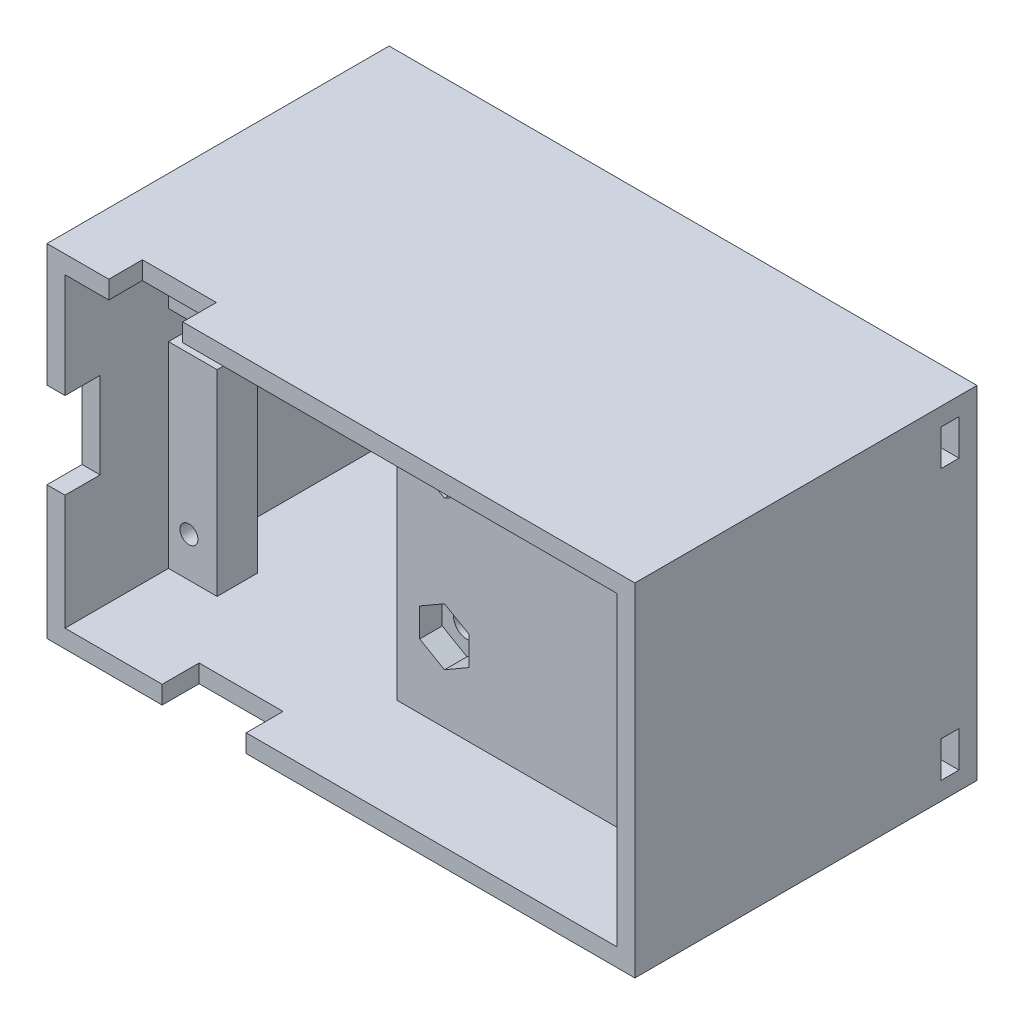
SolidWorks part; units mm, degrees
other "标注1"
sketch "草图16" plane through (3.3763, -43.0665, -26) normal (0.531, -0.7584, -0.3779) x (-0.8474, -0.4776, -0.2321)
other "标注2"
sketch "草图17" plane through (-61.9234, -43.0665, 5.5) normal (-0.5977, -0.3514, 0.7206) x (0.795, -0.3761, 0.4759)
ref_plane "前视基准面" through (0, 0, 0) normal (0, 0, 1) x (1, 0, 0)
ref_plane "上视基准面" through (0, 0, 0) normal (0, 1, 0) x (1, 0, 0)
ref_plane "右视基准面" through (0, 0, 0) normal (1, 0, 0) x (0, 0, -1)
ref_plane "基准面1" through (0, 0, 3.6001) normal (0, 0, 1) x (1, 0, 0)
sketch "草图1" plane through (0, 0, 3.6001) normal (0, 0, 1) x (1, 0, 0)
  line L0 (0.8763, -38.7224) -> (-59.4234, -38.7224) construction
  line L1 (-48.7034, -33.8618) -> (-39.801, -33.8618)
  line L2 (-48.7034, -33.8618) -> (-48.7034, -38.7224)
  line L4 (-39.801, -33.8618) -> (-39.801, -38.7224)
  line L5 (-59.4234, -9.4107) -> (0.8763, -9.4107) construction
  line L7 (-55.7687, -9.4107) -> (-55.7687, -14.2907)
  line L8 (-55.7687, -14.2907) -> (-45.8066, -14.2907)
  line L9 (-45.8066, -9.4107) -> (-45.8066, -14.2907)
  line L10 (-12.699, -17.609) -> (-12.699, -12.109) construction
  line L11 (0.8763, -9.4107) -> (-45.8066, -9.4107)
  line L12 (0.8763, -9.4107) -> (0.8763, -38.7224)
  line L13 (0.8763, -38.7224) -> (-39.801, -38.7224)
  line L14 (-59.4234, -9.4107) -> (-59.4234, -19.2521)
  line L15 (-29.2736, -33.0846) -> (-20.6538, -33.0846)
  line L16 (-29.2736, -33.0846) -> (-29.2736, -36.2921)
  line L17 (-29.2736, -36.2921) -> (-20.6538, -36.2921)
  line L18 (-20.6538, -33.0846) -> (-20.6538, -36.2921)
  line L23 (-12.699, -12.109) -> (-9.399, -12.109)
  line L24 (-12.699, -12.109) -> (-12.699, -17.609)
  line L25 (-12.699, -17.609) -> (-9.399, -17.609)
  line L26 (-9.399, -12.109) -> (-9.399, -17.609)
  line L27 (-48.7034, -38.7224) -> (-59.4234, -38.7224)
  line L28 (-55.7687, -9.4107) -> (-59.4234, -9.4107)
  line L29 (-59.4234, -27.6866) -> (-59.4234, -38.7224)
  line L30 (-59.4234, -19.2521) -> (-54.3557, -19.2521)
  line L32 (-59.4234, -27.6866) -> (-54.3557, -27.6866)
  line L33 (-54.3557, -19.2521) -> (-54.3557, -27.6866)
  circle A0 centre (-57.6581, -36.6498) radius 1
  circle A1 centre (-57.6581, -11.2498) radius 1
  circle A2 centre (-1.016, -11.2498) radius 1
  circle A3 centre (-0.889, -36.8301) radius 1
  circle A4 centre (-4.1259, -29.4689) radius 1.322
  circle A5 centre (-5.9082, -27.2775) radius 0.4462
  circle A6 centre (-4.5737, -26.6799) radius 0.4462
  circle A7 centre (-3.1192, -26.8297) radius 0.4462
  circle A8 centre (-1.9345, -27.6866) radius 0.4462
  circle A9 centre (-1.3369, -29.0211) radius 0.4462
  circle A10 centre (-1.4866, -30.4756) radius 0.4462
  circle A11 centre (-2.3435, -31.6603) radius 0.4462
  circle A12 centre (-3.678, -32.2579) radius 0.4462
  circle A13 centre (-5.1325, -32.1082) radius 0.4462
  circle A14 centre (-6.3173, -31.2513) radius 0.4462
  circle A15 centre (-6.9149, -29.9168) radius 0.4462
  circle A16 centre (-6.7652, -28.4623) radius 0.4462
  point P71 (-4.1259, -29.4689)
  dimension "D1" = 12
ref_plane "基准面2" through (0, 0, -6) normal (0, 0, -1) x (-1, 0, 0)
sketch "草图2" plane through (0, 0, -6) normal (0, 0, -1) x (-1, 0, 0)
  line L0 (29.2736, -9.4107) -> (29.2736, -38.7224) construction
  line L1 (-0.8763, -38.7224) -> (59.4234, -38.7224)
  line L2 (-0.8763, -38.7224) -> (-0.8763, -9.4107)
  line L3 (-0.8763, -9.4107) -> (59.4234, -9.4107)
  line L4 (59.4234, -38.7224) -> (59.4234, -9.4107)
  line L5 (59.4234, -24.0665) -> (-9.3078, -24.0665) construction
  line L6 (-3.3763, -5.0665) -> (61.9234, -43.0665) construction
  line L9 (29.2736, -15.8165) -> (29.2736, -13.1836) construction
  line L10 (27.7854, -15.8165) -> (27.7854, -13.1836)
  line L11 (30.7617, -15.8165) -> (30.7617, -13.1836)
  line L12 (29.2736, -38.7224) -> (29.2736, -43.3487) construction
  line L13 (-3.3763, -43.0665) -> (61.9234, -5.0665) construction
  line L14 (-3.3763, -5.0665) -> (61.9234, -5.0665)
  line L15 (-3.3763, -5.0665) -> (-3.3763, -43.0665)
  line L16 (-3.3763, -43.0665) -> (61.9234, -43.0665)
  line L17 (61.9234, -5.0665) -> (61.9234, -43.0665)
  circle A0 centre (1.016, -11.2498) radius 1
  circle A1 centre (0.889, -36.8301) radius 1
  circle A2 centre (57.6581, -36.6498) radius 1
  circle A3 centre (57.6581, -11.2498) radius 0.9222
  arc A10 (27.7854, -15.8165) -> (30.7617, -15.8165) centre (29.2736, -15.8165) ccw
  arc A11 (30.7617, -13.1836) -> (27.7854, -13.1836) centre (29.2736, -13.1836) ccw
  circle A12 centre (29.2736, -32.3165) radius 1.5
  point P24 (29.2736, -24.0665)
  point P27 (29.2736, -31.5665)
  point P28 (29.2736, -24.0665)
  point P29 (0, 0)
  point P30 (29.2736, -3.8958)
  point P33 (29.2736, -14.5001)
  dimension "D1" = 38
  dimension "D2" = 2.5
  dimension "D3" = 3
  dimension "D4" = 8.25
  dimension "D5" = 2.5
  dimension "D7" = 8.25
extrude "凸台-拉伸2" add sketch "草图2" along normal blind 4.5 separate body contours L17 L14 L15 L16 L4 L1 L2 L3 | L1 L4 L3 L2 A11 L11 A10 L10 A3 A2 A1 A0 region at (-29.281, -24.1116, -6) region at (-29.2736, -5.8221, -6)
sketch "草图3" plane through (0, 0, -6) normal (0, 0, -1) x (-1, 0, 0)
  line L0 (29.2736, -15.8165) -> (29.2736, -10.8487) construction
  line L1 (32.0236, -17.4043) -> (32.0236, -14.2288)
  line L4 (26.5236, -14.2288) -> (26.5236, -17.4043)
  line L5 (26.5236, -17.4043) -> (29.2736, -18.992)
  line L6 (29.2736, -18.992) -> (32.0236, -17.4043)
  line L8 (32.0236, -14.9203) -> (32.0236, -11.7449)
  line L9 (32.0236, -11.7449) -> (29.2736, -10.1572)
  line L10 (29.2736, -10.1572) -> (26.5236, -11.7449)
  line L11 (26.5236, -11.7449) -> (26.5236, -14.9203)
  line L14 (31.8974, -14.9932) -> (32.0236, -14.9203) [skipped]
  line L15 (29.2736, -22.4541) -> (17.663, -22.4541) construction
  line L16 (29.2736, -22.4541) -> (29.2736, -17.3047) construction
  line L17 (26.6497, -14.156) -> (26.5236, -14.2288) [skipped]
  line L18 (26.5236, -14.9203) -> (26.6497, -14.9932) [skipped]
  line L19 (32.0236, -14.2288) -> (31.8974, -14.156) [skipped]
  line L20 (26.5236, -33.9043) -> (29.2736, -35.492)
  line L21 (29.2736, -35.492) -> (32.0236, -33.9043)
  line L22 (32.0236, -33.9043) -> (32.0236, -30.7288)
  line L23 (32.0236, -30.7288) -> (29.2736, -29.1411)
  line L24 (29.2736, -29.1411) -> (26.5236, -30.7288)
  line L25 (26.5236, -30.7288) -> (26.5236, -33.9043)
  arc A0 (26.82, -14.5746) -> (31.7271, -14.5746) centre (29.2736, -15.8165) ccw construction
  arc A1 (31.7271, -14.5746) -> (26.82, -14.5746) centre (29.2736, -13.3326) ccw construction
  circle A2 centre (29.2736, -32.3165) radius 2.75 construction
  circle A3 centre (1.016, -11.2498) radius 1.75
  circle A4 centre (57.6581, -11.2498) radius 1.75
  arc A5 (27.7854, -15.8165) -> (30.7617, -15.8165) centre (29.2736, -15.8165) ccw construction
  circle A6 centre (0.889, -36.8301) radius 1.75
  circle A7 centre (57.6581, -36.6498) radius 1.75
  point P25 (29.2736, -33.8241)
  dimension "D2" = 3.5
  dimension "D1" = 5.5
extrude "切除-拉伸2" cut sketch "草图3" along normal blind 2.5 contours L10 L11 L4 L5 L6 L1 L8 L9 | L24 L25 L20 L21 L22 L23 region at (-29.2736, -14.5746, -6) region at (-29.2736, -32.3165, -6)
sketch "草图5" plane through (0, 0, -10.5) normal (0, 0, -1) x (-1, 0, 0)
  line L0 (29.2736, -7.0665) -> (29.2736, -48.0798) construction
  line L5 (-1.3763, -7.0665) -> (59.9234, -7.0665)
  line L6 (-1.3763, -7.0665) -> (-1.3763, -41.0665)
  line L7 (-1.3763, -41.0665) -> (59.9234, -41.0665)
  line L8 (59.9234, -7.0665) -> (59.9234, -41.0665)
  line L9 (-3.3763, -5.0665) -> (61.9234, -5.0665)
  line L10 (-3.3763, -5.0665) -> (-3.3763, -43.0665)
  line L11 (-3.3763, -43.0665) -> (61.9234, -43.0665)
  line L12 (61.9234, -5.0665) -> (61.9234, -43.0665)
  line L13 (-0.8763, -9.4107) -> (59.4234, -38.7224) construction
  line L14 (-1.3763, -7.0665) -> (59.9234, -41.0665) construction
  line L15 (-3.3763, -5.0665) -> (61.9234, -43.0665) construction
  line L16 (61.9234, -5.0665) -> (-3.3763, -43.0665) construction
  point P12 (29.2736, -24.0665)
  point P13 (29.2736, -24.0665)
  point P18 (29.2736, -24.0665)
  point P19 (0, 0)
  dimension "D1" = 61.2997
  dimension "D2" = 38
  dimension "D3" = 34
  dimension "D4" = 2
extrude "凸台-拉伸3" add sketch "草图5" along normal blind 22 and the other way blind 16
sketch "草图7" plane through (0, -5.0665, 0) normal (0, 1, 0) x (1, 0, 0)
  line L0 (-41.7981, -5.5601) -> (-46.8481, -5.5601) construction
  line L1 (-55.0622, -1.765) -> (-46.8481, -1.765)
  line L2 (-55.0622, -1.765) -> (-55.0622, -5.5601)
  line L3 (-55.0622, -5.5601) -> (-46.8481, -5.5601)
  line L4 (-46.8481, -1.765) -> (-46.8481, -5.5601)
extrude "切除-拉伸4" cut sketch "草图7" against normal blind 3
sketch "草图8" plane through (-61.9234, 0, 0) normal (-1, 0, 0) x (0, 0, 1)
  line L0 (5.6001, -27.6866) -> (5.6001, -38.7224) construction
  line L1 (1.6001, -18.6953) -> (5.6001, -18.6953)
  line L2 (1.6001, -18.6953) -> (1.6001, -28.2708)
  line L3 (1.6001, -28.2708) -> (5.6001, -28.2708)
  line L4 (5.6001, -18.6953) -> (5.6001, -28.2708)
  dimension "D1" = 4
extrude "切除-拉伸5" cut sketch "草图8" against normal blind 3
sketch "草图9" plane through (0, -43.0665, 0) normal (0, -1, 0) x (1, 0, 0)
  line L0 (-59.4234, 5.6001) -> (-48.7034, 5.6001) construction
  line L1 (-49.1273, 5.6001) -> (-39.801, 5.6001)
  line L2 (-49.1273, 5.6001) -> (-49.1273, 1.3978)
  line L3 (-49.1273, 1.3978) -> (-39.801, 1.3978)
  line L4 (-39.801, 5.6001) -> (-39.801, 1.3978)
extrude "切除-拉伸6" cut sketch "草图9" against normal blind 3
sketch "草图13" plane through (0, 0, -6) normal (0, 0, 1) x (1, 0, 0)
  line L2 (-59.9234, -16.0665) -> (-59.9234, -19.2521)
  line L3 (-59.9234, -19.2521) -> (-54.5253, -19.2521)
  line L5 (-59.9234, -16.0665) -> (-54.5253, -16.0665)
  line L6 (-49.1273, -41.0665) -> (-59.9234, -41.0665) construction
  line L7 (-54.5253, -41.0665) -> (-34.5253, -41.0665)
  line L8 (-54.5253, -41.0665) -> (-54.5253, -19.2521)
  line L9 (-54.5253, -7.0665) -> (-34.5253, -7.0665)
  line L10 (-34.5253, -41.0665) -> (-34.5253, -7.0665)
  line L11 (-46.8481, -7.0665) -> (1.3763, -7.0665) construction
  line L12 (-54.5253, -16.0665) -> (-54.5253, -12.8809)
  line L13 (-54.5253, -12.8809) -> (-54.5253, -7.0665)
  dimension "D2" = 20
extrude "切除-拉伸7" cut sketch "草图13" against normal blind 10
sketch "草图15" plane through (0, 0, -10.5) normal (0, 0, -1) x (-1, 0, 0)
  circle A0 centre (1.016, -11.2498) radius 1.75
  circle A1 centre (57.6581, -11.2498) radius 1.75
  circle A2 centre (0.889, -36.8301) radius 1.75
  circle A3 centre (57.6581, -36.6498) radius 1.75
  dimension "D1" = 3.5
extrude "切除-拉伸8" cut sketch "草图15" against normal blind 1.5
sketch "草图18" plane through (0, 0, -32.5) normal (0, 0, -1) x (-1, 0, 0)
  line L0 (59.9234, -7.0665) -> (-1.3763, -7.0665) construction
  line L1 (-1.3763, -6.5665) -> (59.9234, -6.5665)
  line L2 (-1.3763, -6.5665) -> (-1.3763, -41.5665)
  line L3 (-1.3763, -41.5665) -> (59.9234, -41.5665)
  line L4 (59.9234, -6.5665) -> (59.9234, -41.5665)
  line L5 (-1.3763, -41.0665) -> (34.5253, -41.0665) construction
  dimension "D1" = 0.5
  dimension "D2" = 0.5
extrude "切除-拉伸9" cut sketch "草图18" against normal blind 2
sketch "草图19" plane through (1.3763, 0, 0) normal (-1, 0, 0) x (0, 0, 1)
  line L0 (-32.5, -43.0665) -> (-32.5, -5.0665) construction
  line L1 (-30.5, -7.0665) -> (-28.5, -7.0665)
  line L2 (-30.5, -7.0665) -> (-30.5, -11.0665)
  line L3 (-30.5, -11.0665) -> (-28.5, -11.0665)
  line L4 (-28.5, -7.0665) -> (-28.5, -11.0665)
  line L5 (-32.5, -5.0665) -> (5.5, -5.0665) construction
  line L6 (-32.5, -24.0665) -> (15.6063, -24.0665) construction
  line L7 (-30.5, -37.0665) -> (-28.5, -37.0665)
  line L8 (-28.5, -41.0665) -> (-28.5, -37.0665)
  line L9 (-30.5, -41.0665) -> (-28.5, -41.0665)
  line L10 (-30.5, -41.0665) -> (-30.5, -37.0665)
  dimension "D1" = 2
  dimension "D2" = 2
  dimension "D3" = 2
  dimension "D4" = 4
extrude "切除-拉伸10" cut sketch "草图19" against normal blind 2
sketch "草图20" plane through (0, 0, -32.5) normal (0, 0, -1) x (-1, 0, 0)
  line L0 (-1.3763, -24.0665) -> (97.3122, -24.0665) construction
  line L1 (-1.3763, -6.5665) -> (-1.3763, -41.5665) construction
  line L2 (59.9234, -41.5665) -> (59.9234, -6.5665) construction
  line L3 (59.9234, -21.0665) -> (61.9234, -21.0665)
  line L4 (59.9234, -21.0665) -> (59.9234, -27.0665)
  line L5 (59.9234, -27.0665) -> (61.9234, -27.0665)
  line L6 (61.9234, -21.0665) -> (61.9234, -27.0665)
  line L7 (61.9234, -43.0665) -> (61.9234, -5.0665) construction
  line L8 (59.9234, -21.0665) -> (61.9234, -27.0665) construction
  line L9 (61.9234, -21.0665) -> (59.9234, -27.0665) construction
  point P12 (60.9234, -24.0665)
  dimension "D1" = 6
extrude "切除-拉伸11" cut sketch "草图20" against normal blind 1.5
